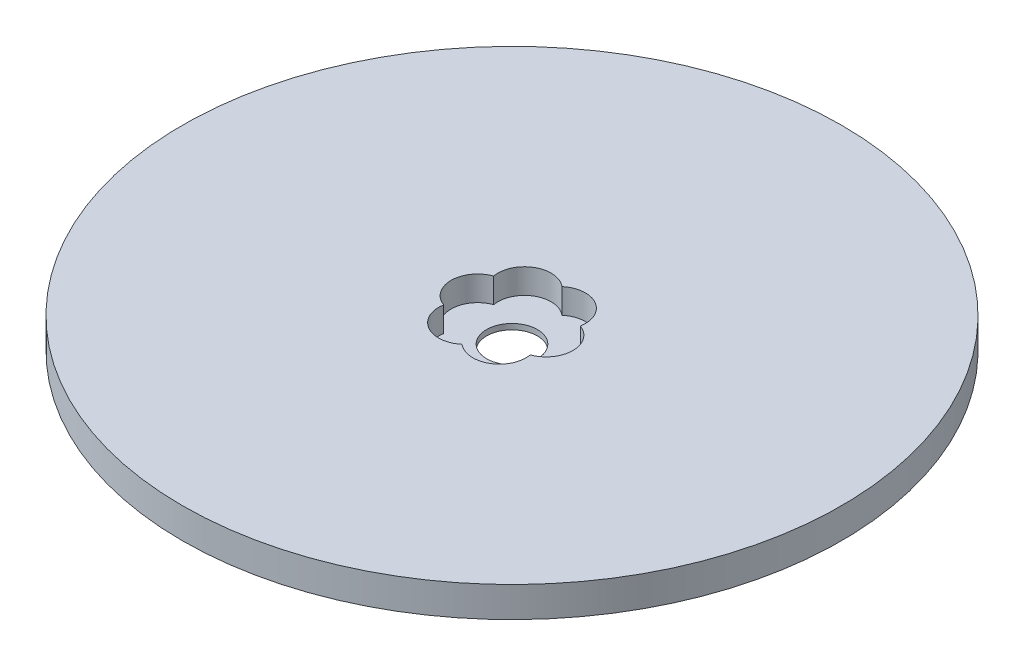
SolidWorks part; units mm, degrees
ref_plane "Front Plane" through (0, 0, 0) normal (0, 0, 1) x (1, 0, 0)
ref_plane "Top Plane" through (0, 0, 0) normal (0, 1, 0) x (1, 0, 0)
ref_plane "Right Plane" through (0, 0, 0) normal (1, 0, 0) x (0, 0, -1)
sketch "Sketch1" plane through (0, 0, 0) normal (0, 1, 0) x (1, 0, 0)
  circle A0 centre (0, 0) radius 65
  dimension "FLANGE_OD" = 130
extrude "Boss-Extrude1" add sketch "Sketch1" along normal blind 6
sketch "Sketch2" plane through (0, 0, 0) normal (0, 1, 0) x (1, 0, 0)
  circle A0 centre (0, 0) radius 5
  dimension "BORE_D" = 10
extrude "Cut-Extrude1" cut sketch "Sketch2" along normal through all
sketch "Sketch3" plane through (0, 6, 0) normal (0, 1, 0) x (1, 0, 0)
  circle A0 centre (0, 0) radius 6.7596 construction
  circle A1 centre (-6.7596, 0) radius 5.2437
  dimension "BOLT_D" = 10.4874
  dimension "BOLT_PCD" = 13.5192
extrude "Cut-Extrude2" cut sketch "Sketch3" against normal blind 4.9014
pattern_circular "CirPattern1" count 6 over 360 about axis through (0, 0, 0) along (0, 1, 0) of "Cut-Extrude2"
